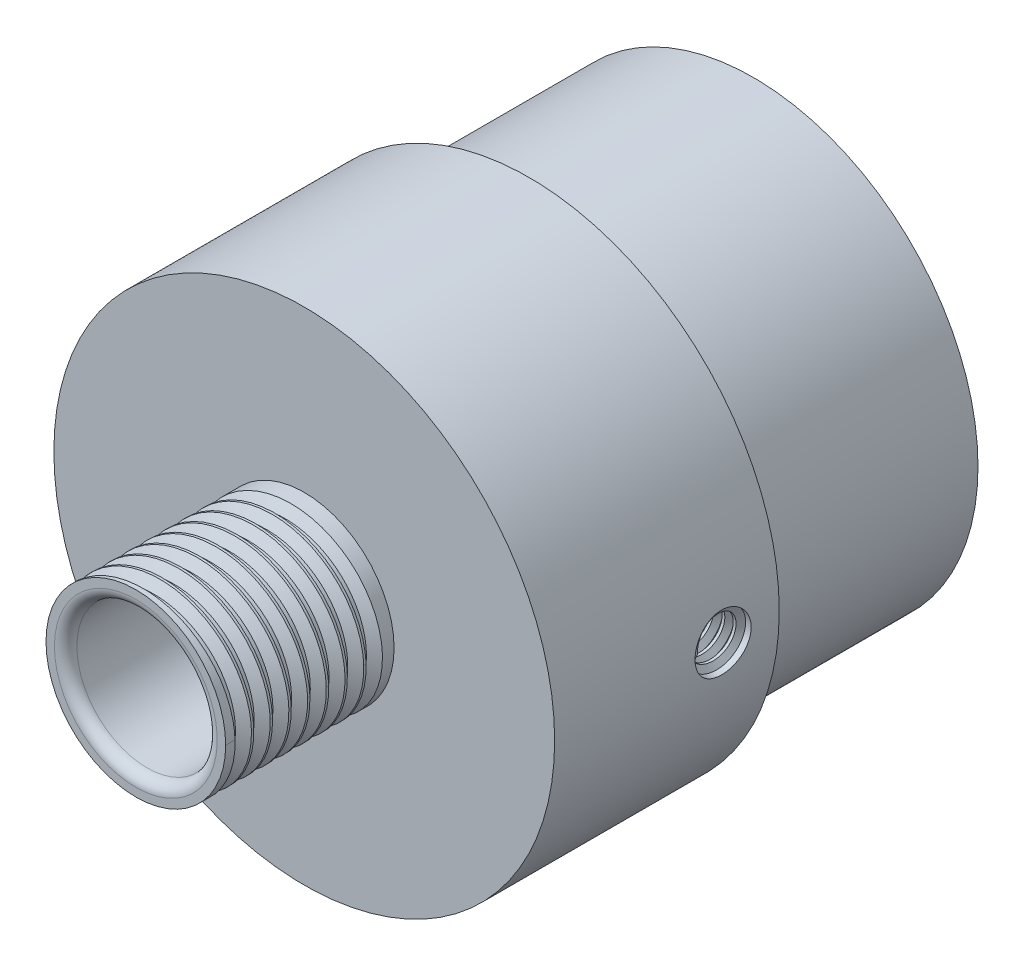
SolidWorks part; units mm, degrees
material "1060 Alloy"
ref_plane "Front Plane" through (0, 0, 0) normal (0, 0, 1) x (1, 0, 0)
ref_plane "Top Plane" through (0, 0, 0) normal (0, 1, 0) x (1, 0, 0)
ref_plane "Right Plane" through (0, 0, 0) normal (1, 0, 0) x (0, 0, -1)
sketch "Sketch1" plane through (0, 0, 0) normal (1, 0, 0) x (0, 0, -1)
  line L0 (-38.1, 0) -> (38.1, 0) construction
  line L1 (-38.1, 7.9375) -> (-13.97, 7.9375)
  line L2 (-13.97, 7.9375) -> (-13.97, 10.16)
  line L3 (-13.97, 10.16) -> (-7.62, 10.16)
  line L4 (-7.62, 10.16) -> (-7.62, 7.9375)
  line L5 (-7.62, 7.9375) -> (26.67, 7.9375)
  line L7 (31.75, 20.32) -> (26.67, 20.32)
  line L8 (26.67, 20.32) -> (26.67, 22.86)
  line L9 (26.67, 22.86) -> (31.75, 22.86)
  line L10 (31.75, 22.86) -> (31.75, 25.4)
  line L12 (31.75, 25.4) -> (6.35, 25.4)
  line L13 (6.35, 25.4) -> (6.35, 28.321)
  line L14 (6.35, 28.321) -> (-19.05, 28.321)
  line L15 (-19.05, 28.321) -> (-19.05, 10.16)
  line L16 (-19.05, 10.16) -> (-38.1, 10.16)
  line L17 (-38.1, 10.16) -> (-38.1, 7.9375)
  line L18 (31.75, 20.32) -> (31.75, 17.78)
  line L19 (31.75, 17.78) -> (26.67, 17.78)
  line L20 (26.67, 17.78) -> (26.67, 7.9375)
  dimension "D1" = 69.85
  dimension "D2" = 44.45
  dimension "D3" = 6.35
  dimension "D4" = 5.08
  dimension "D5" = 2.54
  dimension "D6" = 15.875
  dimension "D7" = 40.64
  dimension "D8" = 50.8
  dimension "D9" = 56.642
  dimension "D10" = 5.08
  dimension "D11" = 2.2225
  dimension "D12" = 19.05
  dimension "D13" = 38.1
other "AlignGroup1"
revolve "Revolve1" add sketch "Sketch1" angle 360 about L0
fillet "Fillet1" radius 1.27 1 edges at (7.9375, 0, 38.1)
thread "Thread1" pitch 2.1167 method cut profile "Thread Profile1" start angle 0, offset 0, length 16.51, pitch 2.1167, diameter 20.32
ref_plane "Plane1" through (-10.16, 0, 38.1) normal (0, -1, 0) x (-1, 0, 0)
sketch "Thread Profile1" plane through (-10.16, 0, 38.1) normal (0, -1, 0) x (-1, 0, 0)
  line L0 (0, 0) -> (0, 2.1167) construction
  line L11 (0, 0) -> (0, 1.8521)
  line L12 (0, 1.8521) -> (-1.1457, 1.1906)
  line L13 (-1.1457, 1.1906) -> (-1.1457, 0.6615)
  line L15 (-1.1457, 0.6615) -> (0, 0)
  line L17 (-1.1457, 0.926) -> (0, 0.926) construction
  point P2 (0, 0)
  dimension "Pitch" = 2.1167
  dimension "Profile_Angle" = 60
  dimension "Profile_Land" = 0.5292
  dimension "Profile_Height" = 1.1457
hole_wizard "#52 (0.25) Diameter Hole1" positions "3DSketch2" profile "Sketch4" hole size "#52" standard "ANSI Inch"
sketch3d "3DSketch2"
  line L0 (0, 0, 0) -> (-21.2806, 0, 0) construction
  point P0 (0, 0, 0)
  point P4 (0, 0, 0)
  point P7 (28.321, 0, 0)
sketch "Sketch4" plane through (28.321, 0, 0) normal (0, 1, 0) x (0, 0, -1)
  line L0 (0, 0) -> (0, 27.3077)
  line L1 (0, 27.3077) -> (3.175, 25.4)
  line L2 (3.175, 25.4) -> (3.175, 0)
  line L5 (3.175, 0) -> (0, 0)
  line L10 (0, 27.3077) -> (-3.175, 25.4) construction
  line L11 (0, -6.35) -> (0, 107.95) construction
  dimension "Hole Dia." = 6.35
  dimension "Hole Depth" = 25.4
  dimension "Drill Angle" = 118
thread "Thread2" pitch 1.27 method extrude profile "Thread Profile3" start angle 0, offset 28.321, length 0, pitch 1.27, diameter 6.35
ref_plane "Plane3" through (28.321, 0, 3.175) normal (0, -1, 0) x (0, 0, 1)
sketch "Thread Profile3" plane through (28.321, 0, 3.175) normal (0, -1, 0) x (0, 0, 1)
  line L0 (0, 0) -> (0, 1.27) construction
  line L11 (0, 0) -> (0, 1.1112)
  line L12 (0, 1.1112) -> (-0.6874, 0.7144)
  line L13 (-0.6874, 0.7144) -> (-0.6874, 0.3969)
  line L15 (-0.6874, 0.3969) -> (0, 0)
  line L17 (-0.6874, 0.5556) -> (0, 0.5556) construction
  point P2 (0, 0)
  dimension "Pitch" = 1.27
  dimension "Profile_Angle" = 60
  dimension "Profile_Land" = 0.3175
  dimension "Profile_Height" = 0.6874
